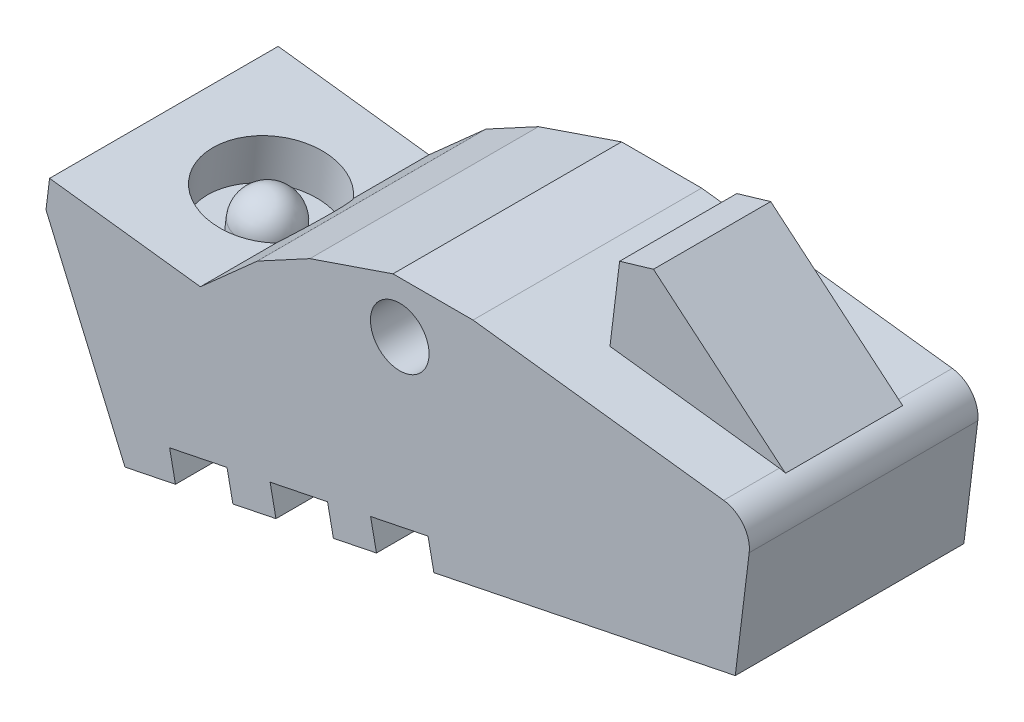
SolidWorks part; units mm, degrees
ref_plane "정면" through (0, 0, 0) normal (0, 0, 1) x (1, 0, 0)
ref_plane "윗면" through (0, 0, 0) normal (0, 1, 0) x (1, 0, 0)
ref_plane "우측면" through (0, 0, 0) normal (1, 0, 0) x (0, 0, -1)
sketch "스케치2" plane through (0, 0, 0) normal (0, 0, 1) x (1, 0, 0)
  line L0 (2.5, 1.75) -> (12.0456, 0.5779)
  line L1 (-12.0703, -2.2794) -> (-9.3754, -8.5326)
  line L2 (-3.0651, 0.7821) -> (-4.8577, -0.1858)
  line L3 (-4.8577, -0.1858) -> (-6.8026, -1.9179)
  line L4 (-0.2309, 1.75) -> (-3.0651, 0.7821)
  line L5 (-9.3754, -8.5326) -> (11.4486, -4.2842)
  line L7 (12.0456, 0.5779) -> (11.4486, -4.2842)
  line L8 (-5.5162, -0.7723) -> (12.5, 1.75) construction
  line L9 (-3.5842, 0.5018) -> (12.5, -1.75) construction
  line L14 (-12.0703, -2.2794) -> (-11.9483, -1.2861)
  line L15 (-11.9483, -1.2861) -> (-6.8026, -1.9179)
  line L19 (-0.2309, 1.75) -> (2.5, 1.75)
  circle A0 centre (0, 0) radius 1
  point P0 (0, 0)
  dimension "D1" = 2
  dimension "D2" = 3.5
  dimension "D5" = 2.5
extrude "보스-돌출2" add sketch "스케치2" along normal blind 7.8 contours L0 A0 | L15 L14 region at (0.0413, -3.0016, 0)
sketch "스케치3" plane through (0.2488, 2.0264, 0) normal (0.1219, 0.9925, 0) x (0.9925, -0.1219, 0)
  line L0 (2.2681, -3.9) -> (12.0621, -3.9) construction
  line L1 (5.0621, -1.9) -> (11.0621, -1.9)
  line L2 (5.0621, -1.9) -> (5.0621, -5.9)
  line L3 (5.0621, -5.9) -> (11.0621, -5.9)
  line L4 (11.0621, -1.9) -> (11.0621, -5.9)
  line L5 (5.0621, -1.9) -> (11.0621, -5.9) construction
  line L6 (5.0621, -5.9) -> (11.0621, -1.9) construction
  point P0 (8.0621, -3.9)
  dimension "D1" = 6
  dimension "D2" = 4
extrude "보스-돌출3" add sketch "스케치3" along normal blind 4
chamfer "모따기1" distance 1.3 distance2 3 1 edges at (5.7607, 5.3797, 3.9) first distance on face at (5.5169, 3.3946, 3.9)
chamfer "모따기2" distance 4 angle 57 1 edges at (11.7159, 4.6485, 3.9) first distance on face at (11.4722, 2.6634, 3.9)
sketch "스케치4" plane through (-0.333, -2.7123, 0) normal (0.1219, 0.9925, 0) x (0.9925, -0.1219, 0)
  line L0 (-11.7025, -3.9) -> (-6.5182, -3.9) construction
  line L1 (-11.7025, -7.8) -> (-11.7025, 0) construction
  line L2 (-6.5182, -7.8) -> (-6.5182, 0) construction
  circle A0 centre (-8.0182, -3.9) radius 2
  dimension "D1" = 4
  dimension "D2" = 1.5
extrude "컷-돌출1" cut sketch "스케치4" against normal mid plane 3
sketch "스케치5" plane through (-0.5158, -4.2011, 0) normal (0.1219, 0.9925, 0) x (0.9925, -0.1219, 0)
  circle A0 centre (-8.0182, -3.9) radius 1
  dimension "D1" = 2
extrude "보스-돌출4" add sketch "스케치5" along normal blind 1.5
fillet "필렛1" radius 1 1 edges at (-9.284, -1.6132, 3.9)
sketch "스케치6" plane through (1.2966, -6.3554, 0) normal (0.1999, -0.9798, 0) x (0.9798, 0.1999, 0)
  line L0 (-10.8918, 7.8) -> (10.3612, 7.8) construction
  line L1 (-9.1339, 7.8) -> (-7.1339, 7.8)
  line L2 (-9.1339, 7.8) -> (-9.1339, 0)
  line L3 (-9.1339, 0) -> (-7.1339, 0)
  line L4 (-7.1339, 7.8) -> (-7.1339, 0)
  line L5 (-10.8918, 0) -> (10.3612, 0) construction
  line L7 (-5.6339, 7.8) -> (-3.6339, 7.8)
  line L8 (-5.6339, 7.8) -> (-5.6339, 0)
  line L9 (-5.6339, 0) -> (-3.6339, 0)
  line L10 (-3.6339, 7.8) -> (-3.6339, 0)
  line L11 (-2.1339, 7.8) -> (-0.1339, 7.8)
  line L12 (-2.1339, 7.8) -> (-2.1339, 0)
  line L13 (-2.1339, 0) -> (-0.1339, 0)
  line L14 (-0.1339, 7.8) -> (-0.1339, 0)
  point P18 (-1.869, -0.1828)
  dimension "D1" = 2
  dimension "D2" = 2
  dimension "D3" = 1.5
  dimension "D4" = 1.5
  dimension "D5" = 2
extrude "컷-돌출2" cut sketch "스케치6" against normal blind 1
fillet "필렛2" radius 1 1 edges at (12.0456, 0.5779, 3.9)
